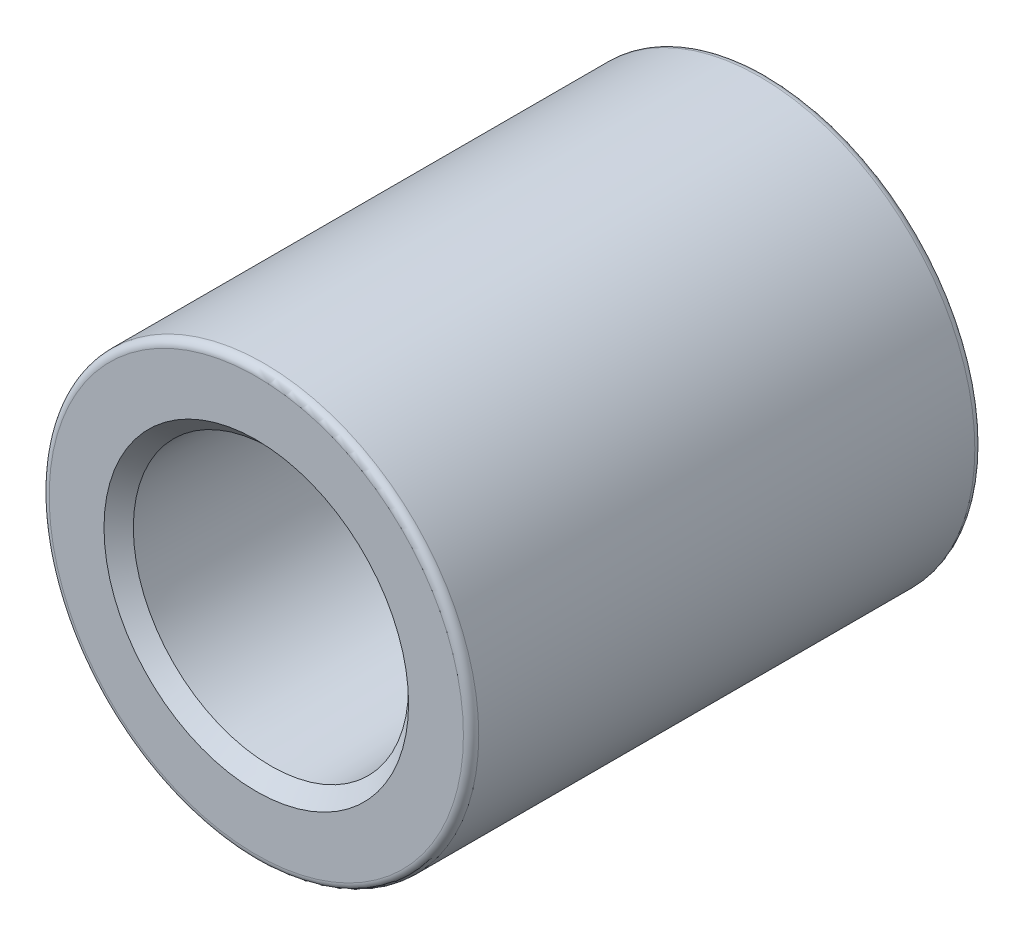
SolidWorks part; units mm, degrees
ref_plane "Front Plane" through (0, 0, 0) normal (0, 0, 1) x (1, 0, 0)
ref_plane "Top Plane" through (0, 0, 0) normal (0, 1, 0) x (1, 0, 0)
ref_plane "Right Plane" through (0, 0, 0) normal (1, 0, 0) x (0, 0, -1)
sketch "Sketch1" plane through (0, 0, 0) normal (0, 0, 1) x (1, 0, 0)
  circle A0 centre (0, 0) radius 10.668
  dimension "A" = 21.336
extrude "Extrude1" add sketch "Sketch1" along normal mid plane 25.4
sketch "Sketch2" plane through (0, 0, 12.7) normal (0, 0, 1) x (1, 0, 0)
  circle A0 centre (0, 0) radius 6.858
  dimension "pipe ID" = 13.716
extrude "Cut-Extrude1" cut sketch "Sketch2" against normal blind 10.2057 draft 1.783
sketch "Sketch3" plane through (0, 0, 2.4943) normal (0, 0, 1) x (1, 0, 0)
  circle A1 centre (0, 0) radius 6.5402
  circle A2 centre (0, 0) radius 6.5402 construction
curve "Helix/Spiral1" parameters "pitch"=1.4111
sketch "Sketch5" plane through (0, 0, 12.7) normal (0, 0, 1) x (1, 0, 0)
  line L0 (0, 7.5636) -> (0, 0) construction
  line L1 (0, 0) -> (-5.3482, 5.3482) construction
  circle A1 centre (0, 0) radius 7.5636
  circle A2 centre (0, 0) radius 6.858 construction
  dimension "D1" = 0.7056
  dimension "D2" = 45
sketch "Sketch4" plane through (0, 0, 0) normal (1, 0, 0) x (0, 0, -1)
  line L0 (-1.8769, 6.5402) -> (-2.4061, 5.6237)
  line L1 (-2.4061, 5.6237) -> (-2.5825, 5.6237)
  line L2 (-2.5825, 5.6237) -> (-3.1773, 6.654)
  line L3 (-1.8769, 6.5402) -> (-3.1116, 6.5402) construction
  line L4 (-1.8769, 6.5402) -> (-3.1773, 6.654)
  line L5 (-2.4943, 5.6237) -> (-2.4943, 6.5402) construction
  line L6 (-2.1415, 6.082) -> (-2.8471, 6.082) construction
  line L7 (-2.4943, 6.5402) -> (-2.4943, -6.5402) construction
  dimension "D1" = 5
  dimension "D2" = 60
  dimension "D3" = 0.1764
  dimension "D4" = 0.7056
sweep "Sweep1" [suppressed] add profiles "Sketch4" path "Helix/Spiral1"
sketch "Sketch6" plane through (0, 0, 12.7) normal (0, 0, 1) x (1, 0, 0)
  circle A1 centre (0, 0) radius 10.668
  circle A2 centre (0, 0) radius 10.668
  dimension "D1" = 0
extrude "Cut-Extrude2" [suppressed] cut sketch "Sketch6" along normal through all
extrude "Cut-Extrude3" cut sketch "Sketch5" against normal blind 3.175 draft 45
ref_axis "Axis1" through (0, 10.4775, 0) along (0, -1, 0)
pattern_circular "CirPattern1" count 2 over 360 about axis through (0, 10.4775, 0) along (0, -1, 0) of "Sweep1", "Cut-Extrude2", "Cut-Extrude3", "Cut-Extrude1"
sketch "Sketch7" plane through (0, 0, 0) normal (0, 0, 1) x (1, 0, 0)
  circle A3 centre (0, 0) radius 7.5636
  circle A4 centre (0, 0) radius 7.5636
  dimension "D2" = 0
extrude "Cut-Extrude4" [suppressed] cut sketch "Sketch7" along normal up to surface and the other way up to surface
fillet "Fillet1" radius 0.381 2 edges at (10.668, 0, -12.7) (10.668, 0, 12.7)
equation "\"D3@Helix/Spiral1\" = \"E@Cut-Extrude1\"+ \"pitch@Helix/Spiral1\""
equation "\"D3@Sketch4\" = \"pitch@Helix/Spiral1\"*.125"
equation "\"D4@Sketch4\" = \"pitch@Helix/Spiral1\"*.5"
equation "\"D1@Sketch5\" = \"pitch@Helix/Spiral1\"*.5"
